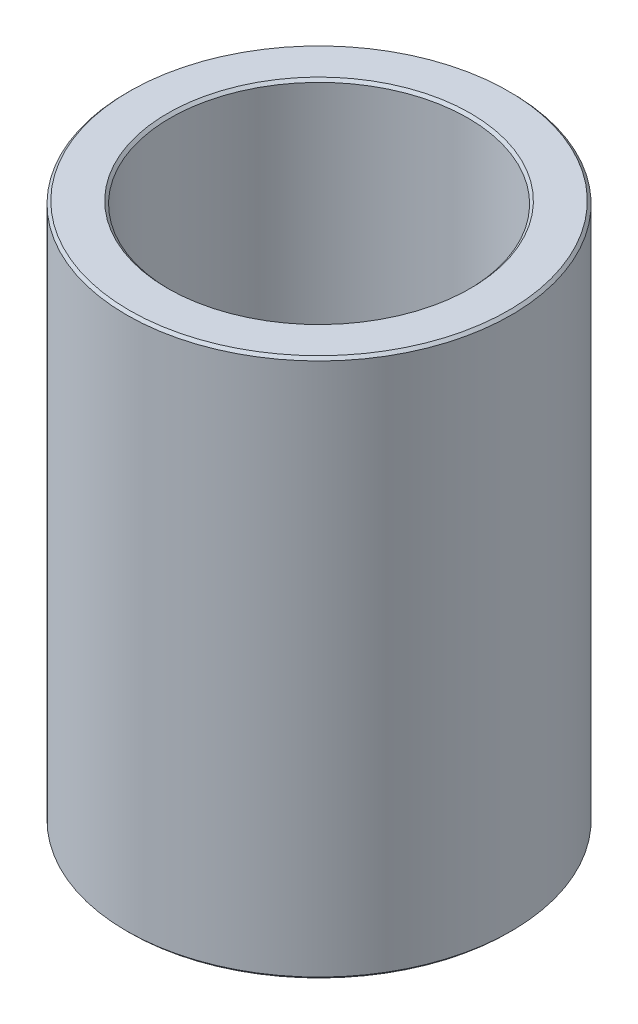
SolidWorks part; units mm, degrees
ref_plane "Front Plane" through (0, 0, 0) normal (0, 0, 1) x (1, 0, 0)
ref_plane "Top Plane" through (0, 0, 0) normal (0, 1, 0) x (1, 0, 0)
ref_plane "Right Plane" through (0, 0, 0) normal (1, 0, 0) x (0, 0, -1)
sketch "Sketch1" plane through (0, 0, 0) normal (0, 1, 0) x (1, 0, 0)
  circle A0 centre (0, 0) radius 57.5
  dimension "SLEEVE_OD" = 115
extrude "Boss-Extrude1" add sketch "Sketch1" along normal blind 161.0726
sketch "Sketch2" plane through (0, 0, 0) normal (0, 1, 0) x (1, 0, 0)
  circle A0 centre (0, 0) radius 44.5001
  dimension "BORE_D" = 89.0002
extrude "Cut-Extrude1" cut sketch "Sketch2" along normal through all
chamfer "Chamfer1" distance 0.8027 angle 45 4 edges at (0, 161.0726, 44.5001) (0, 0, 44.5001) (0, 0, 57.5) (0, 161.0726, 57.5)
